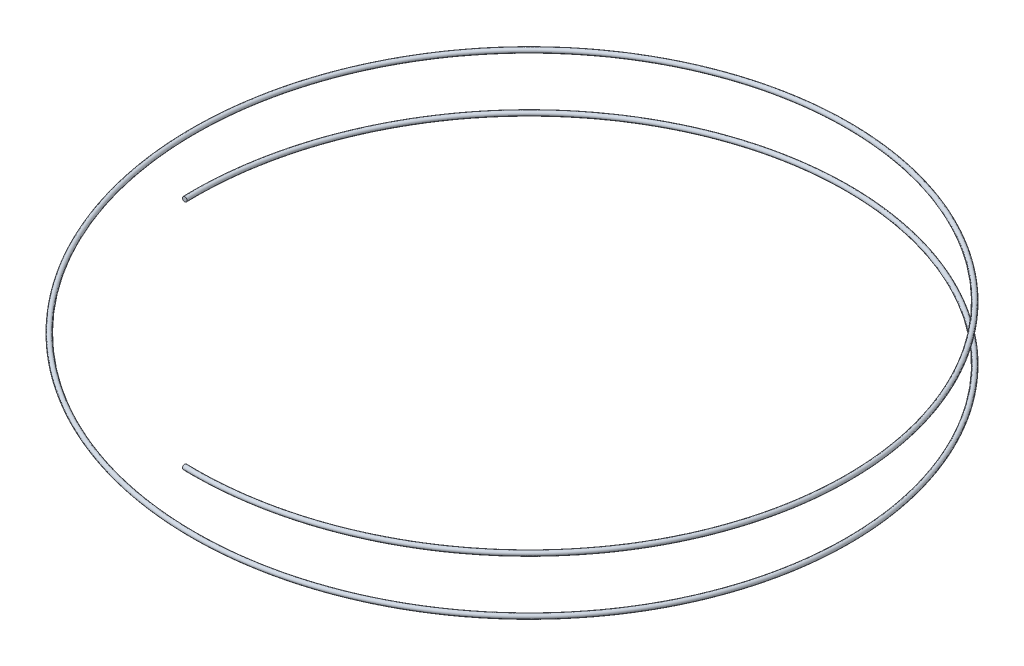
SolidWorks part; units mm, degrees
ref_plane "Alzado" through (0, 0, 0) normal (0, 0, 1) x (1, 0, 0)
ref_plane "Planta" through (0, 0, 0) normal (0, 1, 0) x (1, 0, 0)
ref_plane "Vista lateral" through (0, 0, 0) normal (1, 0, 0) x (0, 0, -1)
sketch "Croquis1" plane through (0, 0, 0) normal (0, 1, 0) x (1, 0, 0)
  circle A0 centre (0, 0) radius 65.9538
curve "Hélice/Espiral1" pitch 11 height 19.25 radius 65.9538 left hand yes centre (0, 0, 0) axis (0, 1, 0) start towards (0, 0, 1)
sketch "Croquis3" plane through (0, 0, 0) normal (0, 0, 1) x (1, 0, 0)
  circle A0 centre (-65.9538, 0) radius 0.4635
  spline S0 degree 3 poles (-65.9538, 0) (-65.9538, 0.1017) (-65.2824, 0.3056) (-62.2918, 0.6111) (-57.4084, 0.9167) (-50.7807, 1.2222) (-42.6101, 1.5278) (-33.1448, 1.8333) (-22.6724, 2.1389) (-11.5111, 2.4444) (0, 2.75) (11.5111, 3.0556) (22.6724, 3.3611) (33.1448, 3.6667) (42.6101, 3.9722) (50.7807, 4.2778) (57.4084, 4.5833) (62.2918, 4.8889) (65.2824, 5.1944) (66.2895, 5.5) (65.2824, 5.8056) (62.2918, 6.1111) (57.4084, 6.4167) (50.7807, 6.7222) (42.6101, 7.0278) (33.1448, 7.3333) (22.6724, 7.6389) (11.5111, 7.9444) (0, 8.25) (-11.5111, 8.5556) (-22.6724, 8.8611) (-33.1448, 9.1667) (-42.6101, 9.4722) (-50.7807, 9.7778) (-57.4084, 10.0833) (-62.2918, 10.3889) (-65.2824, 10.6944) (-66.2895, 11) (-65.2824, 11.3056) (-62.2918, 11.6111) (-57.4084, 11.9167) (-50.7807, 12.2222) (-42.6101, 12.5278) (-33.1448, 12.8333) (-22.6724, 13.1389) (-11.5111, 13.4444) (0, 13.75) (11.5111, 14.0556) (22.6724, 14.3611) (33.1448, 14.6667) (42.6101, 14.9722) (50.7807, 15.2778) (57.4084, 15.5833) (62.2918, 15.8889) (65.2824, 16.1944) (66.2895, 16.5) (65.2824, 16.8056) (62.2918, 17.1111) (57.4084, 17.4167) (50.7807, 17.7222) (42.61, 18.0278) (33.1449, 18.3333) (22.6718, 18.6389) (11.5133, 18.9444) (3.8322, 19.1483) (0, 19.25) knots 0 0 0 0 0.015873 0.031746 0.047619 0.063492 0.079365 0.095238 0.111111 0.126984 0.142857 0.15873 0.174603 0.190476 0.206349 0.222222 0.238095 0.253968 0.269841 0.285714 0.301587 0.31746 0.333333 0.349206 0.365079 0.380952 0.396825 0.412698 0.428571 0.444444 0.460317 0.47619 0.492063 0.507937 0.52381 0.539683 0.555556 0.571429 0.587302 0.603175 0.619048 0.634921 0.650794 0.666667 0.68254 0.698413 0.714286 0.730159 0.746032 0.761905 0.777778 0.793651 0.809524 0.825397 0.84127 0.857143 0.873016 0.888889 0.904762 0.920635 0.936508 0.952381 0.968254 0.984127 1 1 1 1 construction
sweep "Barrer1" add profiles "Croquis3" path "Hélice/Espiral1"
